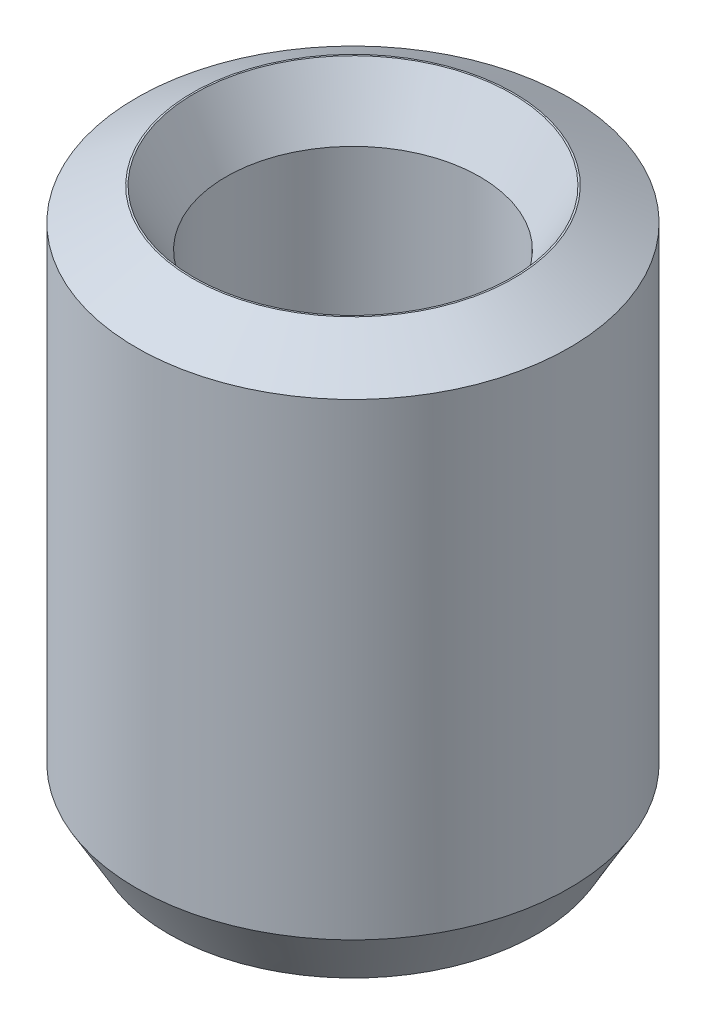
SolidWorks part; units mm, degrees
ref_plane "Front Plane" through (0, 0, 0) normal (0, 0, 1) x (1, 0, 0)
ref_plane "Top Plane" through (0, 0, 0) normal (0, 1, 0) x (1, 0, 0)
ref_plane "Right Plane" through (0, 0, 0) normal (1, 0, 0) x (0, 0, -1)
sketch "Sketch1" plane through (0, 0, 0) normal (0, 1, 0) x (1, 0, 0)
  circle A0 centre (0, 0) radius 25
  dimension "SLEEVE_OD" = 50
extrude "Boss-Extrude1" add sketch "Sketch1" along normal blind 64.2095
sketch "Sketch2" plane through (0, 0, 0) normal (0, 1, 0) x (1, 0, 0)
  circle A0 centre (0, 0) radius 14.6561
  dimension "BORE_D" = 29.3123
extrude "Cut-Extrude1" cut sketch "Sketch2" along normal through all
chamfer "Chamfer1" distance 3.7169 angle 60 4 edges at (0, 64.2095, 14.6561) (0, 0, 14.6561) (0, 0, 25) (0, 64.2095, 25) first distance on face at (0, 64.2095, 14.6561) first distance on face at (0, 0, 14.6561) first distance on face at (0, 64.2095, 25)
